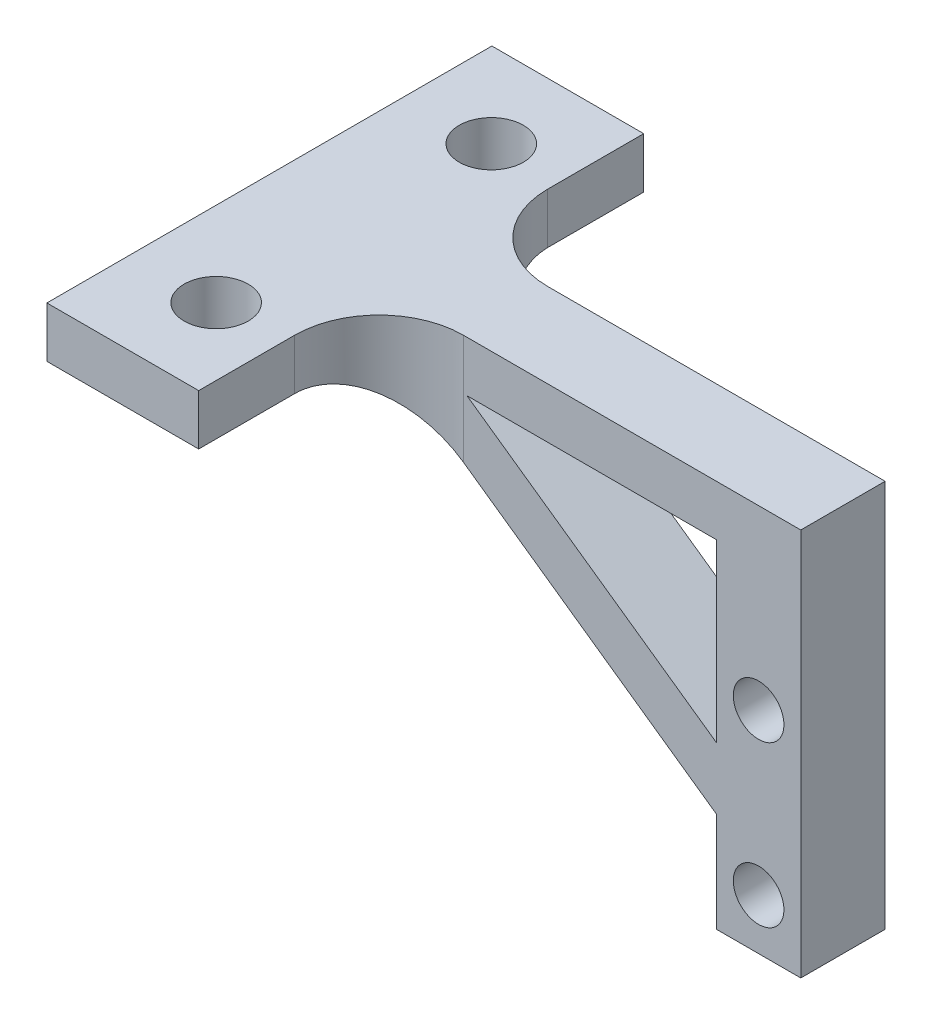
SolidWorks part; units mm, degrees
ref_plane "Front Plane" through (0, 0, 0) normal (0, 0, 1) x (1, 0, 0)
ref_plane "Top Plane" through (0, 0, 0) normal (0, 1, 0) x (1, 0, 0)
ref_plane "Right Plane" through (0, 0, 0) normal (1, 0, 0) x (0, 0, -1)
sketch "Sketch1" plane through (0, 0, 0) normal (0, 1, 0) x (1, 0, 0)
  line L0 (0, 0) -> (0, 16.31) construction
  line L1 (0, 8.155) -> (-5, 8.155) construction
  line L2 (-5, -5.035) -> (4, -5.035)
  line L3 (-5, -5.035) -> (-5, 21.345)
  line L4 (-5, 21.345) -> (4, 21.345)
  line L5 (4, -5.035) -> (4, 21.345)
  circle A0 centre (0, 0) radius 1.9
  circle A1 centre (0, 16.31) radius 1.9
  dimension "D1" = 3.8
  dimension "D2" = 16.31
  dimension "D3" = 5
  dimension "D4" = 4
  dimension "D5" = 26.38
extrude "body mount" add sketch "Sketch1" along normal blind 3
sketch "Sketch2" plane through (4, 0, 0) normal (1, 0, 0) x (0, 0, -1)
  line L0 (-5.035, 0) -> (21.345, 0) construction
  line L1 (10.655, 0) -> (5.655, 0)
  line L2 (10.655, 0) -> (10.655, 3)
  line L3 (10.655, 3) -> (5.655, 3)
  line L4 (5.655, 0) -> (5.655, 3)
  line L5 (-5.035, 3) -> (21.345, 3) construction
  line L6 (8.155, 3) -> (8.155, 0) construction
  dimension "D1" = 5
extrude "Boss-Extrude2" add sketch "Sketch2" along normal blind 25
sketch "Sketch3" plane through (0, 0, 0) normal (0, -1, 0) x (1, 0, 0)
  line L0 (29, -10.655) -> (4, -10.655) construction
  line L1 (29, -5.655) -> (24, -5.655)
  line L2 (29, -5.655) -> (29, -10.655)
  line L3 (29, -10.655) -> (24, -10.655)
  line L4 (24, -5.655) -> (24, -10.655)
  dimension "D1" = 5
extrude "Boss-Extrude3" add sketch "Sketch3" along normal blind 20
sketch "Sketch4" plane through (0, 0, -10.655) normal (0, 0, -1) x (-1, 0, 0)
  line L0 (-26.5, -20) -> (-26.5, -4.5881) construction
  line L1 (-24, -20) -> (-29, -20) construction
  circle A0 centre (-26.5, -17) radius 1.5
  circle A1 centre (-26.5, -7.5) radius 1.5
  dimension "D1" = 3
  dimension "D2" = 9.5
  dimension "D3" = 3
extrude "Cut-Extrude1" cut sketch "Sketch4" against normal blind 20
ref_plane "Plane1" through (0, 0, -8.155) normal (0, 0, -1) x (-1, 0, 0)
sketch "Sketch5" plane through (0, 0, -8.155) normal (0, 0, -1) x (-1, 0, 0)
  line L0 (-6.6052, 0) -> (-24, -12.25) construction
  line L1 (-24, -20) -> (-24, 0) construction
  line L2 (-26.5, -17) -> (-26.5, -7.5) construction
  line L3 (-26.5, -12.25) -> (-24, -12.25) construction
  line L4 (-24, -10.4154) -> (-9.2103, 0)
  line L5 (-24, 0) -> (-4, 0) construction
  line L6 (-24, -14.0846) -> (-4, 0)
  line L7 (-4, 0) -> (5, 0) construction
  line L8 (-24, -14.0846) -> (-24, -10.4154)
  line L9 (-9.2103, 0) -> (-4, 0)
  dimension "D1" = 3
extrude "Boss-Extrude4" add sketch "Sketch5" along normal up to surface and the other way up to surface up to face at (25, -7.5, -10.655) other way up to face at (26.5, -6, -5.655)
fillet "Fillet2" radius 5 2 edges
